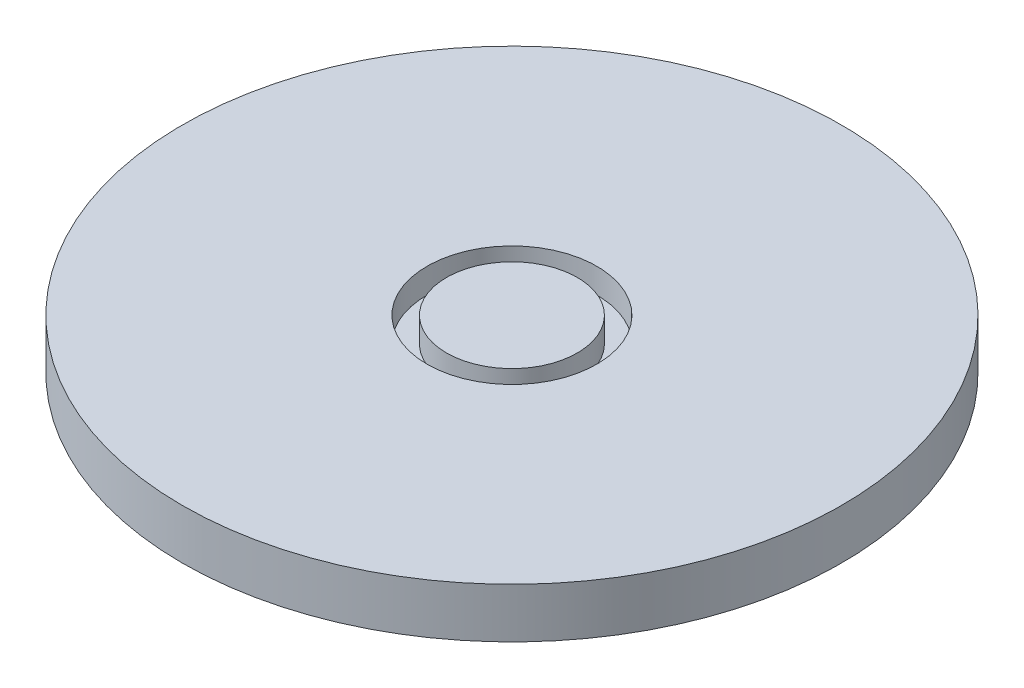
SolidWorks part; units mm, degrees
ref_plane "Front Plane" through (0, 0, 0) normal (0, 0, 1) x (1, 0, 0)
ref_plane "Top Plane" through (0, 0, 0) normal (0, 1, 0) x (1, 0, 0)
ref_plane "Right Plane" through (0, 0, 0) normal (1, 0, 0) x (0, 0, -1)
sketch "Sketch1" plane through (0, 0, 0) normal (0, 1, 0) x (1, 0, 0)
  line L0 (0, -2.55) -> (0, 2.04) construction
  line L1 (-1.53, 2.04) -> (1.53, 2.04)
  circle A0 centre (0, 0) radius 2.55
  circle A1 centre (0, 0) radius 6.55
  circle A2 centre (0, 0) radius 33
  circle A3 centre (0, 0) radius 8.5
  point P10 (0, 2.04)
  dimension "D1" = 4
extrude "Boss-Extrude1" add sketch "Sketch1" along normal blind 2.5 and the other way blind 2.5 contours A2 A3 region at (-32.0666, 0, 0)
extrude "Boss-Extrude2" add sketch "Sketch1<4>" along normal blind 2.5 separate body contours L0 A0 L1 | A0 L0 L1 region at (-1.1097, 0, 0.1233) region at (1.1097, 0, 0.1233)
sketch "Sketch1<4>" plane through (0, 0, 0) normal (0, 1, 0) x (1, 0, 0) same geometry as "Sketch1"
extrude "Boss-Extrude3" add sketch "Sketch1<5>" along normal blind 2.5 and the other way blind 15 contours L1 A0 | A1 A0 region at (0, 0, -2.2459) region at (-6.3647, 0, 0)
sketch "Sketch1<5>" plane through (0, 0, 0) normal (0, 1, 0) x (1, 0, 0) same geometry as "Sketch1"
extrude "Boss-Extrude4" add sketch "Sketch1<6>" against normal blind 5 contours A3 A1 region at (-8.2596, 0, 0)
sketch "Sketch1<6>" plane through (0, 0, 0) normal (0, 1, 0) x (1, 0, 0) same geometry as "Sketch1"
ref_plane "Plane1" through (0, -8.1, 0) normal (0, 1, 0) x (1, 0, 0)
sketch "Sketch2" plane through (0, -8.1, 0) normal (0, 1, 0) x (1, 0, 0)
  line L0 (1.53, 2.04) -> (-1.53, 2.04)
  circle A0 centre (0, 0) radius 8.5
  circle A2 centre (0, 0) radius 2.55
  point P6 (0, 2.04)
  point P11 (0, 2.04)
ref_plane "Plane2" through (0, -15, 0) normal (0, -1, 0) x (-1, 0, 0)
extrude "Boss-Extrude5" add sketch "Sketch2" along normal up to surface (-6.9 mm away) contours A0 A2 region at (-8.2596, -8.1, 0) up to face at (0, -15, 0.255)
fillet "Fillet1" radius 2 1 edges at (0, -2.5, 8.5)
sketch "Sketch3" plane through (0, -8.1, 0) normal (0, 1, 0) x (1, 0, 0)
  circle A0 centre (0, 0) radius 6.55
  ellipse E0 centre (0, 0) end of major axis (5.5154, 5.5154) minor radius 1.6
  ellipse E1 centre (-0.0448, 0.0378) end of major axis (-5.5603, 5.5532) minor radius 1.6
  ellipse E2 centre (0, 0) end of major axis (7.8, 0) minor radius 1.6
  ellipse E3 centre (-0.005, 0.0584) end of major axis (-0.005, 7.8584) minor radius 1.6
extrude "Boss-Extrude6" add sketch "Sketch3" along normal blind 3.01 contours A0 E3 | A0 E1 | A0 E2 | A0 E0 | A0 E3 | A0 E1 | A0 E2 | A0 E0 region at (7.0416, -8.1, 0) region at (4.9792, -8.1, -4.9792) region at (4.9591, -8.1, 4.9665) region at (-0.0052, -8.1, -7.0649) region at (-0.0052, -8.1, 7.0184) region at (-4.9993, -8.1, -4.9919) region at (-4.9792, -8.1, 4.9792) region at (-7.0416, -8.1, 0)
